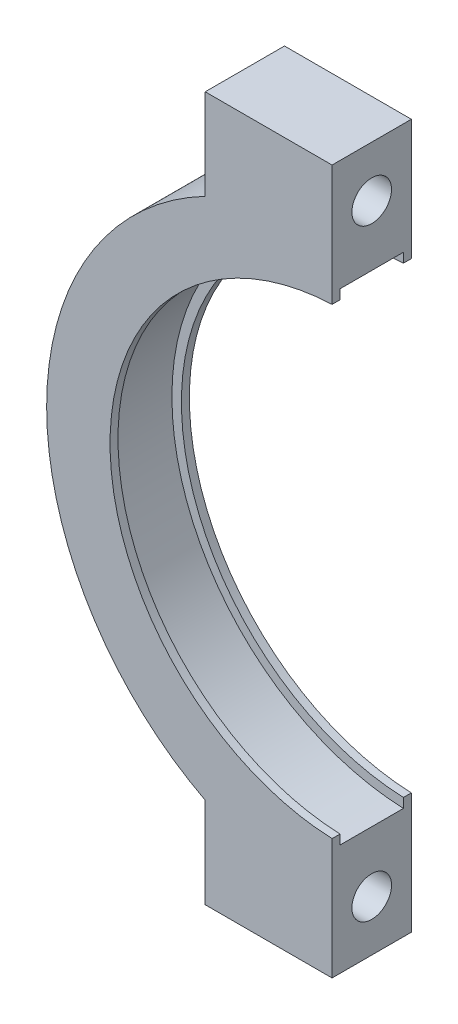
SolidWorks part; units mm, degrees
material "Tungsten"
ref_plane "Front Plane" through (0, 0, 0) normal (0, 0, 1) x (1, 0, 0)
ref_plane "Top Plane" through (0, 0, 0) normal (0, 1, 0) x (1, 0, 0)
ref_plane "Right Plane" through (0, 0, 0) normal (1, 0, 0) x (0, 0, -1)
sketch "Sketch1" plane through (0, 0, 0) normal (0, 0, 1) x (1, 0, 0)
  line L0 (0, 0) -> (0, -23699.5554) construction
  line L1 (0, 0) -> (-23699.5554, 0) construction
  line L2 (-3, 111) -> (-3, 72.9383)
  line L3 (-3, -72.9383) -> (-3, -111)
  line L5 (-3, 111) -> (-43, 111)
  line L6 (-43, 111) -> (-43, 82.4621)
  line L8 (-3, -111) -> (-43, -111)
  line L9 (-43, -111) -> (-43, -82.4621)
  arc A0 (-43, 82.4621) -> (-43, -82.4621) centre (0, 0) ccw
  arc A1 (-3, 75.9408) -> (-3, -75.9408) centre (0, 0) ccw
  arc A2 (-3, 72.9383) -> (-3, -72.9383) centre (0, 0) ccw
  point P5 (-3, 0)
  point P11 (0, 0)
  point P13 (0, 0)
  point P15 (0, 0)
  point P20 (-3, 24.8038)
  point P21 (9.4185, 0)
  point P22 (0, 0)
  point P23 (0, 0)
  dimension "D2" = 93
  dimension "D3" = 152
  dimension "D4" = 146
  dimension "D1" = 3
  dimension "D5" = 3
  dimension "D6" = 222
  dimension "D7" = 40
extrude "Boss-Extrude1" add sketch "Sketch1" along normal blind 25 contours A1 L2 L5 L6 A0 L9 L8 L3 | A2 L2 A1 L3 region at (-5.3955, 93.4704, 0) region at (-4.6851, 74.4395, 0)
sketch "Sketch2" plane through (-3, 0, 0) normal (1, 0, 0) x (0, 0, -1)
  line L0 (-25, 111) -> (0, 111) construction
  line L1 (0, 0) -> (-40.0524, 0) construction
  circle A0 centre (-12.5, 95) radius 6.25
  circle A1 centre (-12.5, -95) radius 6.25
  point P7 (-12.5, 111)
  dimension "D1" = 12.5
  dimension "D2" = 190
extrude "Cut-Extrude1" cut sketch "Sketch2" against normal through all
extrude "Cut-Extrude2" cut sketch "Sketch1<3>" along normal blind 20 from offset 2.5 contours A2 L2 A1 L3 region at (-4.6851, 74.4395, 0)
sketch "Sketch1<3>" plane through (0, 0, 0) normal (0, 0, 1) x (1, 0, 0) same geometry as "Sketch1"
